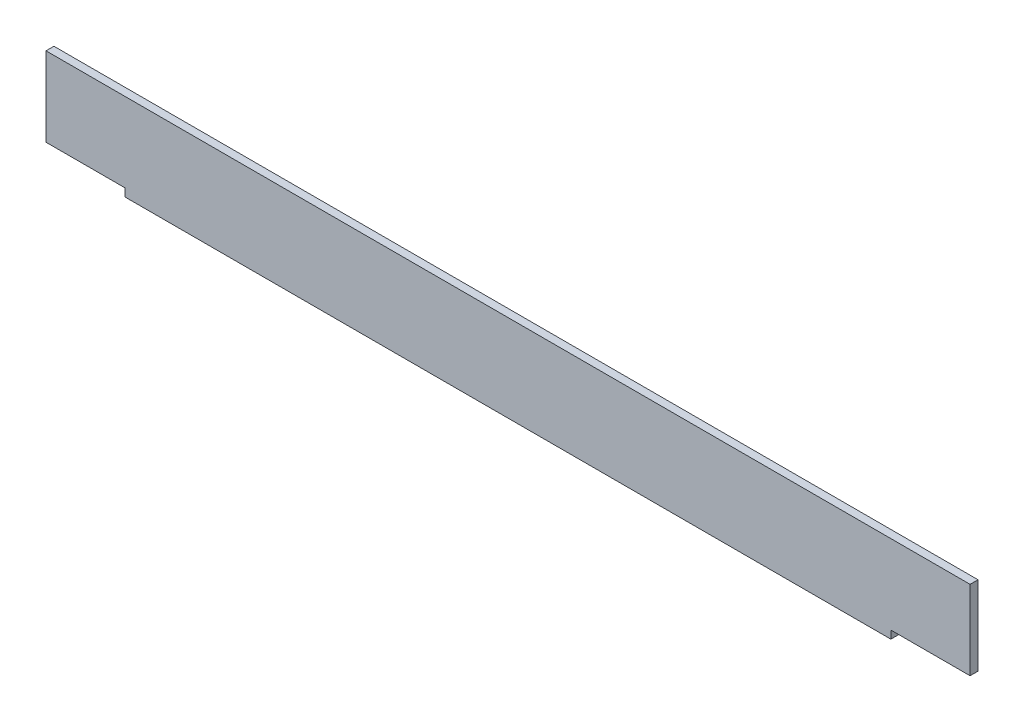
SolidWorks part; units mm, degrees
ref_plane "Спереди" through (0, 0, 0) normal (0, 0, 1) x (1, 0, 0)
ref_plane "Сверху" through (0, 0, 0) normal (0, 1, 0) x (1, 0, 0)
ref_plane "Справа" through (0, 0, 0) normal (1, 0, 0) x (0, 0, -1)
sketch "Эскиз1" plane through (0, 0, 0) normal (1, 0, 0) x (0, 0, -1)
  line L0 (0, 33) -> (0, 0)
  line L1 (0, 0) -> (33, 0)
extrude "Вытянуть-Тонкостенный1" add sketch "Эскиз1" along normal blind 350 thin thin type one direction reverse wall 3
sketch "Эскиз2" plane through (0, 0, 0) normal (0, -1, 0) x (1, 0, 0)
  line L0 (350, -33) -> (0, -33) construction
  line L1 (0, -33) -> (30, -33)
  line L2 (0, -33) -> (0, 0)
  line L3 (0, 0) -> (30, 0)
  line L4 (30, -33) -> (30, 0)
  line L5 (175, -33) -> (175, 23.8308) construction
  line L6 (320, -33) -> (320, 0)
  line L7 (350, 0) -> (320, 0)
  line L8 (350, -33) -> (350, 0)
  line L9 (350, -33) -> (320, -33)
extrude "Вырез-Вытянуть1" cut sketch "Эскиз2" against normal blind 3
